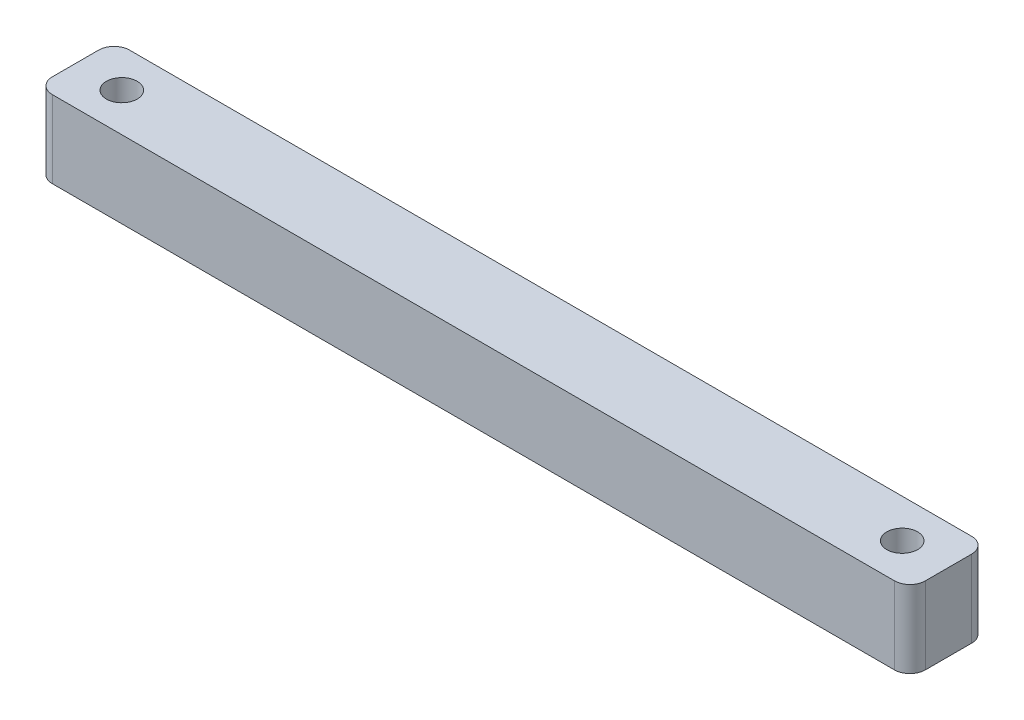
SolidWorks part; units mm, degrees
material "1060 Alloy"
ref_plane "Front Plane" through (0, 0, 0) normal (0, 0, 1) x (1, 0, 0)
ref_plane "Top Plane" through (0, 0, 0) normal (0, 1, 0) x (1, 0, 0)
ref_plane "Right Plane" through (0, 0, 0) normal (1, 0, 0) x (0, 0, -1)
sketch "Sketch2" plane through (0, 0, 0) normal (0, 0, 1) x (1, 0, 0)
  line L1 (-28.2843, 2.5) -> (28.2843, 2.5)
  line L2 (-28.2843, 2.5) -> (-28.2843, -2.5)
  line L3 (-28.2843, -2.5) -> (28.2843, -2.5)
  line L4 (28.2843, 2.5) -> (28.2843, -2.5)
  line L5 (-28.2843, 2.5) -> (28.2843, -2.5) construction
  line L6 (-28.2843, -2.5) -> (28.2843, 2.5) construction
  point P0 (0, 0)
  dimension "D1" = 5
  dimension "D2" = 56.5685
extrude "Boss-Extrude1" add sketch "Sketch2" along normal blind 5
sketch "Sketch3" plane through (0, 2.5, 0) normal (0, 1, 0) x (1, 0, 0)
  line L0 (-28.2843, -2.5) -> (28.2843, -2.5) construction
  line L1 (-28.2843, -5) -> (-28.2843, 0) construction
  line L2 (28.2843, -5) -> (28.2843, 0) construction
  circle A0 centre (-25.2843, -2.5) radius 1
  circle A1 centre (25.2843, -2.5) radius 1
  dimension "D2" = 2
  dimension "D4" = 2
  dimension "D1" = 3
  dimension "D3" = 3
extrude "Cut-Extrude1" cut sketch "Sketch3" against normal through all
fillet "Fillet1" radius 1 4 edges at (-28.2843, 0, 5) (-28.2843, 0, 0) (28.2843, 0, 5) (28.2843, 0, 0)
